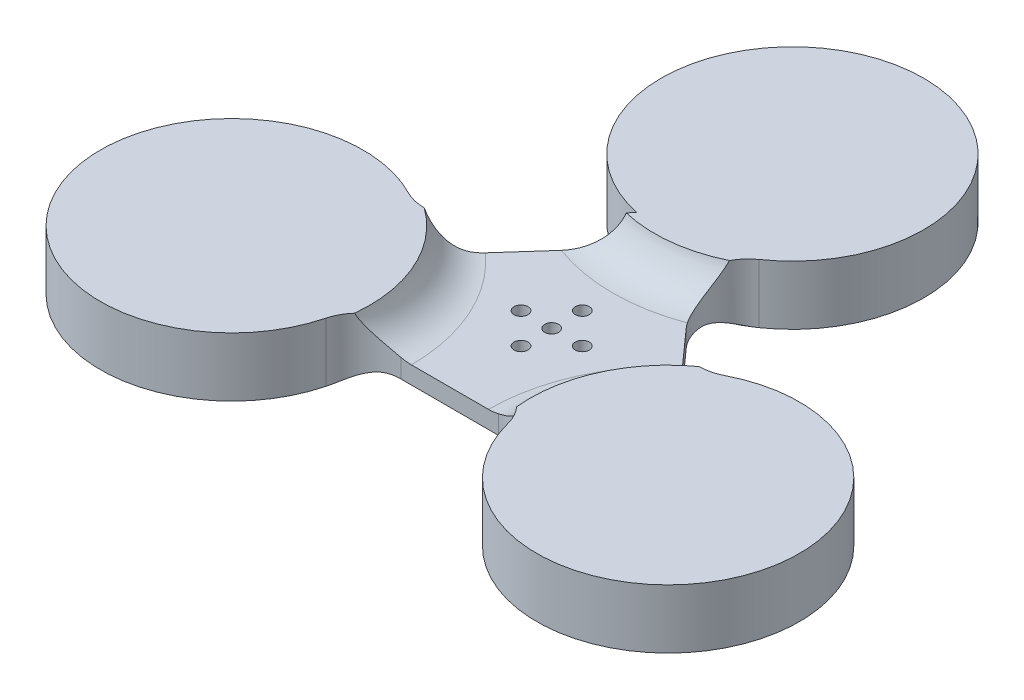
SolidWorks part; units mm, degrees
ref_plane "Front Plane" through (0, 0, 0) normal (0, 0, 1) x (1, 0, 0)
ref_plane "Top Plane" through (0, 0, 0) normal (0, 1, 0) x (1, 0, 0)
ref_plane "Right Plane" through (0, 0, 0) normal (1, 0, 0) x (0, 0, -1)
sketch "草图1" plane through (0, 0, 0) normal (0, 1, 0) x (1, 0, 0)
  line L0 (0, 0) -> (-43.9457, 0) construction
  line L1 (0, 0) -> (0, 55) construction
  line L2 (0, 0) -> (-49.8469, -23.244) construction
  line L3 (0, 0) -> (49.8469, -23.244) construction
  line L4 (-49.8469, 6.756) -> (-28.8627, 46.8182) construction
  line L5 (28.8627, 46.8182) -> (49.8469, 6.756) construction
  line L6 (-30.2338, -45.9447) -> (30.2338, -45.9447) construction
  line L7 (-29.8654, -0.8668) -> (-6.1912, 25.6458)
  line L8 (29.8654, -0.8668) -> (6.1912, 25.6458)
  line L9 (-19.8469, -23.244) -> (19.8469, -23.244)
  circle A0 centre (0, 0) radius 1.6
  circle A1 centre (0, 0) radius 7 construction
  circle A2 centre (-7, 0) radius 1.6
  circle A3 centre (0, 0) radius 55 construction
  circle A4 centre (0, 55) radius 28.5
  circle A5 centre (-49.8469, -23.244) radius 28.5
  circle A6 centre (49.8469, -23.244) radius 28.5
  circle A7 centre (0, 7) radius 1.6
  circle A8 centre (7, 0) radius 1.6
  circle A9 centre (0, -7) radius 1.6
  circle A10 centre (-49.8469, -23.244) radius 30
  circle A11 centre (49.8469, -23.244) radius 30
  circle A12 centre (0, 55) radius 30
  point P23 (0, 0)
  dimension "D1" = 3.2
  dimension "D2" = 14
  dimension "D3" = 3.2
  dimension "D4" = 110
  dimension "D5" = 57
  dimension "D7" = 60
  dimension "D8" = 25
  dimension "D9" = 25
  dimension "D6" = 4
extrude "凸台-拉伸1" add sketch "草图1" along normal blind 15 contours A12 L4 A10 L6 A11 L5 A9 A8 A7 A2 A0 | A11 A6 | A10 A5 | A12 A4 region at (-17.4525, 0, -11.8754) region at (-23.2403, 0, 11.332) region at (-18.3634, 0, -77.6405) region at (23.2403, 0, 11.332)
sketch "草图3" plane through (0, 15, 0) normal (0, 1, 0) x (1, 0, 0)
  circle A0 centre (-49.8469, -23.244) radius 29
  circle A1 centre (49.8469, -23.244) radius 29
  circle A2 centre (0, 55) radius 29
extrude "凸台-拉伸2" add sketch "草图3" against normal blind 2
chamfer "倒角1" distance 3 angle 45 3 edges at (49.8469, 0, 51.744) (0, 0, -26.5) (-49.8469, 0, 51.744)
sketch "草图4" plane through (0, 0, 0) normal (0, -1, 0) x (1, 0, 0)
  line L3 (7.3342, -24.3657) -> (28.8663, -0.252)
  line L4 (7.3342, -24.3657) -> (28.8663, -0.252)
  line L5 (18.3469, 23.244) -> (-18.3469, 23.244)
  line L9 (18.3469, 23.244) -> (-18.3469, 23.244)
  line L10 (-28.8663, -0.252) -> (-7.3342, -24.3657)
  line L11 (-28.8663, -0.252) -> (-7.3342, -24.3657)
  circle A0 centre (0, 0) radius 3
  circle A1 centre (0, -7) radius 1.6
  circle A2 centre (-7, 0) radius 1.6
  arc A3 (18.3469, 23.244) -> (28.8663, -0.252) centre (49.8469, 23.244) ccw
  arc A4 (-28.8663, -0.252) -> (-18.3469, 23.244) centre (-49.8469, 23.244) ccw
  arc A5 (7.3342, -24.3657) -> (-7.3342, -24.3657) centre (0, -55) ccw
  arc A6 (18.3469, 23.244) -> (28.8663, -0.252) centre (49.8469, 23.244) ccw
  arc A7 (-28.8663, -0.252) -> (-18.3469, 23.244) centre (-49.8469, 23.244) ccw
  arc A8 (7.3342, -24.3657) -> (-7.3342, -24.3657) centre (0, -55) ccw
  circle A9 centre (0, 7) radius 1.6
  circle A10 centre (7, 0) radius 1.6
  point P24 (0, 0)
  dimension "D3" = 6
  dimension "D1" = 0
  dimension "D2" = 4
extrude "切除-拉伸1" cut sketch "草图4" against normal blind 10 from offset 8 contours A8 L11 A7 L9 A6 L4 offset against normal yes
fillet "圆角1" radius 10 5 edges at (-29.8654, 8.25, 0.8668) (-19.8469, 8.25, 23.244) (19.8469, 8.25, 23.244) (29.8654, 8.25, 0.8668) (6.1912, 8.25, -25.6458)
fillet "圆角2" radius 10 3 edges at (21.0968, 8, 10.3723) (3.485, 8, -23.6934) (-21.0968, 8, 10.3723)
sketch "草图5" plane through (0, 0, 0) normal (0, -1, 0) x (1, 0, 0)
  line L1 (-7.3342, -24.3657) -> (-6.1912, -25.6458)
  line L2 (-7.3342, -24.3657) -> (-6.1912, -25.6458)
  line L3 (15.2998, -15.4452) -> (24.0509, -5.6448)
  line L4 (11.1171, 23.244) -> (-11.1171, 23.244)
  line L5 (-24.0509, -5.6448) -> (-7.3342, -24.3657)
  line L6 (15.2998, -15.4452) -> (24.0509, -5.6448)
  line L7 (11.1171, 23.244) -> (-11.1171, 23.244)
  line L8 (-24.0509, -5.6448) -> (-7.3342, -24.3657)
  arc A0 (-20.7996, 30.744) -> (-36.0942, -3.418) centre (-49.8469, 23.244) cw
  arc A1 (36.0942, -3.418) -> (20.7996, 30.744) centre (49.8469, 23.244) cw
  arc A2 (-6.1912, -25.6458) -> (17.0691, -30.3293) centre (0, -55) cw
  arc A3 (-6.1912, -25.6458) -> (17.0691, -30.3293) centre (0, -55) ccw
  arc A4 (-20.7996, 30.744) -> (-36.0942, -3.418) centre (-49.8469, 23.244) ccw
  arc A5 (-31.4224, -2.3057) -> (-36.0942, -3.418) centre (-31.51, -12.3053) ccw
  arc A6 (-31.4224, -2.3057) -> (-18.5176, 26.5185) centre (-49.8469, 23.244) ccw
  arc A7 (-20.7996, 30.744) -> (-18.5176, 26.5185) centre (-11.1171, 33.244) ccw
  arc A8 (31.4224, -2.3057) -> (24.0509, -5.6448) centre (31.51, -12.3053) ccw
  arc A9 (18.5176, 26.5185) -> (31.4224, -2.3057) centre (49.8469, 23.244) ccw
  arc A10 (11.1171, 23.244) -> (18.5176, 26.5185) centre (11.1171, 33.244) ccw
  arc A11 (-18.5176, 26.5185) -> (-11.1171, 23.244) centre (-11.1171, 33.244) ccw
  arc A12 (-31.4224, -2.3057) -> (-18.5176, 26.5185) centre (-49.8469, 23.244) ccw
  arc A13 (-24.0509, -5.6448) -> (-31.4224, -2.3057) centre (-31.51, -12.3053) ccw
  arc A14 (13.8915, -26.7285) -> (-7.3342, -24.3657) centre (0, -55) ccw
  arc A15 (15.2998, -15.4452) -> (13.8915, -26.7285) centre (22.7588, -22.1057) ccw
  arc A16 (31.4224, -2.3057) -> (24.0509, -5.6448) centre (31.51, -12.3053) ccw
  arc A17 (18.5176, 26.5185) -> (31.4224, -2.3057) centre (49.8469, 23.244) ccw
  arc A18 (11.1171, 23.244) -> (18.5176, 26.5185) centre (11.1171, 33.244) ccw
  arc A19 (-18.5176, 26.5185) -> (-11.1171, 23.244) centre (-11.1171, 33.244) ccw
  arc A20 (-31.4224, -2.3057) -> (-18.5176, 26.5185) centre (-49.8469, 23.244) ccw
  arc A21 (-24.0509, -5.6448) -> (-31.4224, -2.3057) centre (-31.51, -12.3053) ccw
  arc A22 (13.8915, -26.7285) -> (-7.3342, -24.3657) centre (0, -55) ccw
  arc A23 (15.2998, -15.4452) -> (13.8915, -26.7285) centre (22.7588, -22.1057) ccw
  arc A24 (-20.7996, 30.744) -> (-36.0942, -3.418) centre (-49.8469, 23.244) ccw
  arc A25 (-31.4224, -2.3057) -> (-36.0942, -3.418) centre (-31.51, -12.3053) ccw
  arc A26 (-31.4224, -2.3057) -> (-18.5176, 26.5185) centre (-49.8469, 23.244) ccw
  arc A27 (-20.7996, 30.744) -> (-18.5176, 26.5185) centre (-11.1171, 33.244) ccw
  arc A28 (36.0942, -3.418) -> (20.7996, 30.744) centre (49.8469, 23.244) ccw
  arc A29 (18.5176, 26.5185) -> (20.7996, 30.744) centre (11.1171, 33.244) ccw
  arc A30 (18.5176, 26.5185) -> (31.4224, -2.3057) centre (49.8469, 23.244) ccw
  arc A31 (36.0942, -3.418) -> (31.4224, -2.3057) centre (31.51, -12.3053) ccw
  arc A32 (36.0942, -3.418) -> (20.7996, 30.744) centre (49.8469, 23.244) ccw
  arc A33 (18.5176, 26.5185) -> (20.7996, 30.744) centre (11.1171, 33.244) ccw
  arc A34 (18.5176, 26.5185) -> (31.4224, -2.3057) centre (49.8469, 23.244) ccw
  arc A35 (36.0942, -3.418) -> (31.4224, -2.3057) centre (31.51, -12.3053) ccw
  arc A36 (13.8915, -26.7285) -> (17.0691, -30.3293) centre (22.7588, -22.1057) ccw
  arc A37 (13.8915, -26.7285) -> (-7.3342, -24.3657) centre (0, -55) ccw
  arc A38 (-6.1912, -25.6458) -> (17.0691, -30.3293) centre (0, -55) ccw
  arc A39 (13.8915, -26.7285) -> (17.0691, -30.3293) centre (22.7588, -22.1057) ccw
  arc A40 (13.8915, -26.7285) -> (-7.3342, -24.3657) centre (0, -55) ccw
  line M24 (15.2998, -15.4452) -> (24.0509, -5.6448)
  arc M25 (24.0509, -5.6448) -> (31.4224, -2.3057) centre (31.51, -12.3053) cw
  arc M26 (31.4224, -2.3057) -> (18.5176, 26.5185) centre (49.8469, 23.244) cw
  arc M27 (18.5176, 26.5185) -> (11.1171, 23.244) centre (11.1171, 33.244) cw
  line M28 (11.1171, 23.244) -> (-11.1171, 23.244)
  arc M29 (-11.1171, 23.244) -> (-18.5176, 26.5185) centre (-11.1171, 33.244) cw
  arc M30 (-18.5176, 26.5185) -> (-31.4224, -2.3057) centre (-49.8469, 23.244) cw
  arc M31 (-31.4224, -2.3057) -> (-24.0509, -5.6448) centre (-31.51, -12.3053) cw
  line M32 (-24.0509, -5.6448) -> (-7.3342, -24.3657)
  arc M33 (-7.3342, -24.3657) -> (13.8915, -26.7285) centre (0, -55) cw
  arc M34 (13.8915, -26.7285) -> (15.2998, -15.4452) centre (22.7588, -22.1057) cw
  circle M35 centre (0, 7) radius 1.6
  circle M36 centre (7, 0) radius 1.6
  circle M37 centre (0, -7) radius 1.6
  circle M38 centre (-7, 0) radius 1.6
  circle M39 centre (0, 0) radius 1.6
  dimension "D1" = 0
  dimension "D2" = 0
  dimension "D3" = 0
  dimension "D4" = 0
extrude "切除-拉伸2" cut sketch "草图5" against normal blind 4 contours A27 A0 A25 M30 | A39 L2 A2 M33 | M34 M24 M25 M26 M27 M28 M29 M30 M31 M32 M33 M35 M37 M39 M38 M36 | A35 A1 A33 M26 region at (4.2295, 0, -25.236) region at (-15.0782, 0, -14.4566) region at (-33.9152, 0, -2.2028) region at (21.4482, 0, 10.5296)
fillet "圆角3" radius 10 3 edges at (5.9217, 4, -25.5902) (22.4659, 4, 10.9852) (-22.4659, 4, 10.9852)
